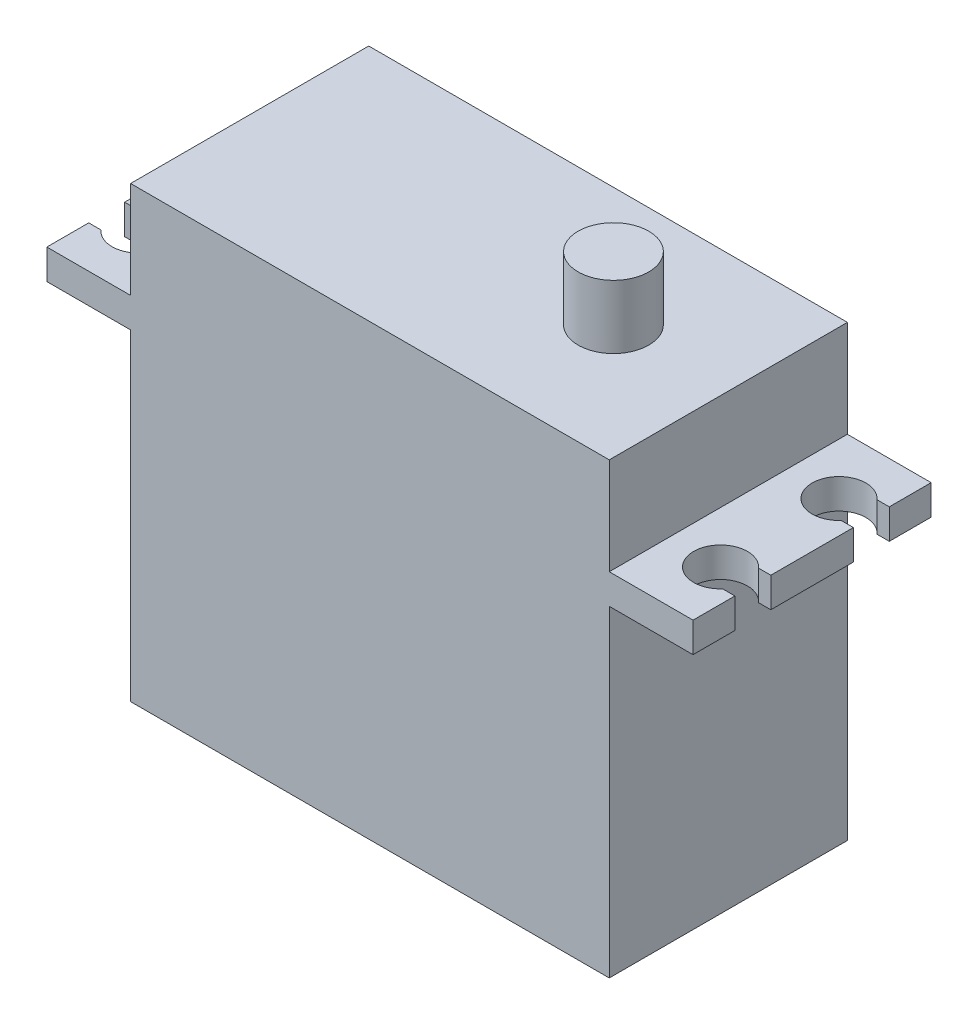
SolidWorks part; units mm, degrees
other "Axis"
other "Body"
material "Nylon 101"
ref_plane "Front Plane" through (0, 0, 0) normal (0, 0, 1) x (1, 0, 0)
ref_plane "Top Plane" through (0, 0, 0) normal (0, 1, 0) x (1, 0, 0)
ref_plane "Right Plane" through (0, 0, 0) normal (1, 0, 0) x (0, 0, -1)
sketch "Sketch1" plane through (0, 0, 0) normal (0, 1, 0) x (1, 0, 0)
  line L1 (-20, -9.95) -> (20, -9.95)
  line L2 (-20, -9.95) -> (-20, 9.95)
  line L3 (-20, 9.95) -> (20, 9.95)
  line L4 (20, -9.95) -> (20, 9.95)
  line L5 (-20, -9.95) -> (20, 9.95) construction
  line L6 (-20, 9.95) -> (20, -9.95) construction
  point P0 (0, 0)
  dimension "D1" = 40
  dimension "D2" = 19.9
extrude "Boss-Extrude1" add sketch "Sketch1" along normal blind 26.9
sketch "Sketch4" plane through (0, 26.9, 0) normal (0, 1, 0) x (1, 0, 0)
  line L0 (27, 6.45) -> (-27, 6.45) construction
  line L1 (-27, -9.95) -> (27, -9.95)
  line L2 (-27, -9.95) -> (-27, -6.45)
  line L3 (-27, 9.95) -> (27, 9.95)
  line L4 (27, -9.95) -> (27, -6.45)
  line L5 (-27, -9.95) -> (27, 9.95) construction
  line L6 (-27, 9.95) -> (27, -9.95) construction
  line L7 (-24.3, -4.95) -> (24.3, -4.95) construction
  line L8 (-24.3, -4.95) -> (-24.3, 4.95) construction
  line L9 (-24.3, 4.95) -> (24.3, 4.95) construction
  line L10 (24.3, -4.95) -> (24.3, 4.95) construction
  line L11 (-24.3, -4.95) -> (24.3, 4.95) construction
  line L12 (-24.3, 4.95) -> (24.3, -4.95) construction
  line L13 (-27, 3.45) -> (27, 3.45) construction
  line L14 (-27, -3.45) -> (27, -3.45) construction
  line L15 (-27, -6.45) -> (27, -6.45) construction
  line L16 (-25.9771, 6.45) -> (-27, 6.45)
  line L17 (-25.9771, 3.45) -> (-27, 3.45)
  line L18 (-25.9771, -3.45) -> (-27, -3.45)
  line L19 (-25.9771, -6.45) -> (-27, -6.45)
  line L20 (25.9771, 6.45) -> (27, 6.45)
  line L21 (25.9771, 3.45) -> (27, 3.45)
  line L22 (25.9771, -3.45) -> (27, -3.45)
  line L23 (25.9771, -6.45) -> (27, -6.45)
  line L24 (-27, -3.45) -> (-27, 3.45)
  line L25 (-27, 6.45) -> (-27, 9.95)
  line L26 (27, 6.45) -> (27, 9.95)
  line L27 (27, -3.45) -> (27, 3.45)
  arc A0 (25.9771, 6.45) -> (25.9771, 3.45) centre (24.3, 4.95) ccw
  arc A1 (25.9771, -3.45) -> (25.9771, -6.45) centre (24.3, -4.95) ccw
  arc A2 (-25.9771, 3.45) -> (-25.9771, 6.45) centre (-24.3, 4.95) ccw
  arc A3 (-25.9771, -6.45) -> (-25.9771, -3.45) centre (-24.3, -4.95) ccw
  point P0 (0, 0)
  point P14 (0, 0)
  dimension "D3" = 4.5
  dimension "D1" = 54
  dimension "D2" = 19.9
  dimension "D4" = 48.6
  dimension "D5" = 9.9
  dimension "D6" = 3
  dimension "D7" = 3
extrude "Boss-Extrude2" add sketch "Sketch4" along normal blind 2.5
sketch "Sketch5" plane through (0, 29.4, 0) normal (0, 1, 0) x (1, 0, 0)
  line L1 (-20, -9.95) -> (20, -9.95)
  line L2 (-20, -9.95) -> (-20, 9.95)
  line L3 (-20, 9.95) -> (20, 9.95)
  line L4 (20, -9.95) -> (20, 9.95)
  line L5 (-20, -9.95) -> (20, 9.95) construction
  line L6 (-20, 9.95) -> (20, -9.95) construction
  point P0 (0, 0)
extrude "Boss-Extrude3" add sketch "Sketch5" along normal blind 8.1
sketch "Sketch8" plane through (0, 0, 0) normal (0, 0, 1) x (1, 0, 0)
  line L0 (10.4, 42.8) -> (10.4, 3)
  line L1 (-20, 26.9) -> (-20, 0) construction
  line L2 (10.4, 42.8) -> (13.35, 42.8)
  line L3 (13.35, 42.8) -> (13.35, 25)
  line L4 (13.35, 25) -> (16.4, 25)
  line L5 (16.4, 25) -> (16.4, 3)
  line L6 (16.4, 3) -> (10.4, 3)
  dimension "D1" = 30.4
  dimension "D2" = 2.95
  dimension "D3" = 42.8
  dimension "D4" = 22
  dimension "D5" = 6
  dimension "D6" = 3
revolve "Cut-Revolve1" cut sketch "Sketch8" angle 360 about L0
revolve "Revolve1" add sketch "Sketch8<2>" angle 360 about L0
sketch "Sketch8<2>" plane through (0, 0, 0) normal (0, 0, 1) x (1, 0, 0) same geometry as "Sketch8"
